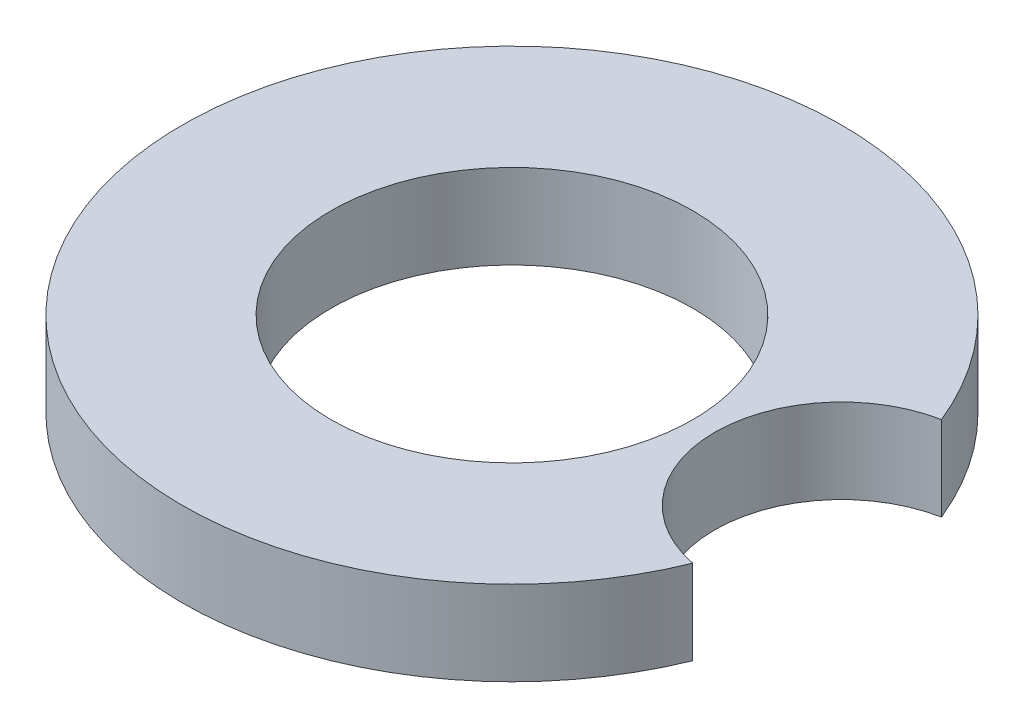
SolidWorks part; units mm, degrees
ref_plane "Front Plane" through (0, 0, 0) normal (0, 0, 1) x (1, 0, 0)
ref_plane "Top Plane" through (0, 0, 0) normal (0, 1, 0) x (1, 0, 0)
ref_plane "Right Plane" through (0, 0, 0) normal (1, 0, 0) x (0, 0, -1)
sketch "Sketch1" plane through (0, 0, 0) normal (0, 1, 0) x (1, 0, 0)
  circle A0 centre (0, 0) radius 27.2
  circle A1 centre (0, 0) radius 49.53
  dimension "Front_CR_ID" = 54.4
  dimension "Front_CR_OD" = 99.06
extrude "Boss-Extrude1" add sketch "Sketch1" along normal blind 12.7 contours A1
extrude "Cut-Extrude2" cut sketch "Sketch1<10>" along normal through all contours A0
sketch "Sketch1<10>" plane through (0, 0, 0) normal (0, 1, 0) x (1, 0, 0) same geometry as "Sketch1"
sketch "Sketch2" plane through (0, 12.7, 0) normal (0, 1, 0) x (1, 0, 0)
  circle A2 centre (49.53, 0) radius 19.05
  circle A3 centre (0, 0) radius 49.53 construction
  dimension "D1" = 38.1
extrude "Cut-Extrude3" cut sketch "Sketch2" against normal through all contours A2
ref_plane "Plane1" through (0, 6.35, 0) normal (0, -1, 0) x (-1, 0, 0)
equation "\"Motor_OD\" = 54.4mm"
equation "\"Aft_Section_Length\" = 32in"
equation "\"Mid_Coupler_Length\" = 12in"
equation "\"AB_Coupler_OD_Length\"= 1in"
equation "\"AB_Coupling_Section_Length\"= 0.375in"
equation "\"AB_Coupler_Length\"= \"AB_Coupler_OD_Length\" + \"AB_Coupling_Section_Length\" * 2"
equation "\"Cutout_Angle\" = 60"
equation "\"AB_Paddle_Height\" = 0.375in"
equation "\"AB_Coupler_Num_Screws\"= 4"
equation "\"Num_Cutouts\" = 4"
equation "\"AB_Coupler_OD\"= 4.024in"
equation "\"AB_Coupler_ID\"= 3.7in"
equation "\"AB_Coupler_Surface_Diameter\"= 3.899in"
equation "\"AB_Coupling_Screw_Diameter\"= 0.1065in"
equation "\"AB_Central_Bushing_Length\" = 0.75in"
equation "\"Lead_Screw_Dist\" = 2in"
equation "\"Lead_Screw_Diam\" = 0.375in"
equation "\"Lead_Screw_Length\" = \"Mid_Coupler_Length\" + 2*0.375in + 2*0.5in"
equation "\"Paddle_Pin_Offset\" = 0.25in"
equation "\"Paddle_Pin_Radius\" = 2.25*2/3in"
equation "\"Paddle_Gear_OD\" = 3.2in"
equation "\"Fwd_BKHD_From_Top\" = 18in"
equation "\"Front_CR_ID@Sketch1\"=\"Motor_OD\""
equation "\"Body_Tube_OD\"= 4.024in"
equation "\"Body_Tube_ID\"= 3.90in"
equation "\"Coupler_OD\" = 3.899in"
equation "\"Coupler_ID\" = 3.755in"
equation "\"Fwd_Section_Length\" = 20in"
equation "\"Mid_Section_Length\" = 4in"
equation "\"Aft_Upper_Tube_Length\" = 10in"
equation "\"Aft_Lower_Tube_Length\" = 18in"
equation "\"Nosecone_Coupler_Length\" = 5in"
equation "\"Avionics_Bulkhead_Thickness\" = 0.25in"
equation "\"Avionics_Bulkhead_Lip\" = 0.125in"
equation "\"Avionics_Board_Length\" = \"Mid_Coupler_Length\" - 2*\"Avionics_Bulkhead_Lip\""
equation "\"Lead_Screw_Hole_Diam\" = 0.386in"
equation "\"Front_CR_OD@Sketch1\"=\"Body_Tube_ID\""
equation "\"Centering_Ring_Cutout_Dia\"=1.5in"
equation "\"D1@Sketch2\"=\"Centering_Ring_Cutout_Dia\""
